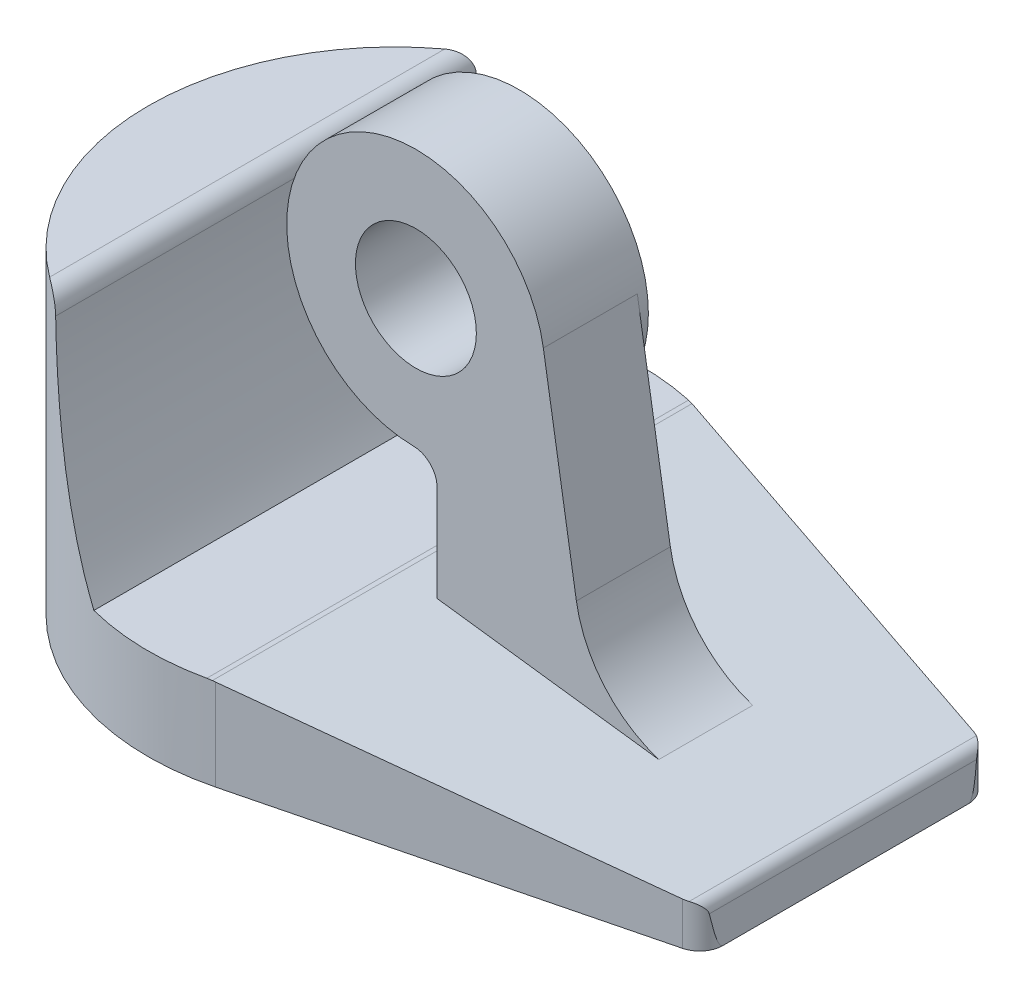
SolidWorks part; units mm, degrees
ref_plane "Front Plane" through (0, 0, 0) normal (0, 0, 1) x (1, 0, 0)
ref_plane "Top Plane" through (0, 0, 0) normal (0, 1, 0) x (1, 0, 0)
ref_plane "Right Plane" through (0, 0, 0) normal (1, 0, 0) x (0, 0, -1)
sketch "Sketch1" plane through (0, 0, 0) normal (0, 1, 0) x (1, 0, 0)
  line L0 (2.56, 10.1832) -> (18.4438, 6.1901)
  line L1 (19.2, 5.2203) -> (19.2, -5.2203)
  line L2 (18.4438, -6.1901) -> (2.56, -10.1832)
  line L3 (0, 0) -> (-30.4312, 0) construction
  circle A0 centre (0, 0) radius 10.5
  arc A1 (19.2, -5.2203) -> (18.4438, -6.1901) centre (18.2, -5.2203) cw
  arc A2 (18.4438, 6.1901) -> (19.2, 5.2203) centre (18.2, 5.2203) cw
  point P6 (19.2, 0)
  point P9 (19.2, -6)
  point P13 (19.2, 6)
  point P15 (0, -10.5)
  dimension "D1" = 21
  dimension "D4" = 1
  dimension "D3" = 29.7
  dimension "D2" = 12
extrude "Boss-Extrude1" add sketch "Sketch1" along normal blind 13.5 contours A2 L0 A0 L2 A1 L1 | A0 | A0 A1 L2 | A0 L0 A2 region at (13.6045, 0, 0) region at (0, 0, 0)
sketch "Sketch2" plane through (0, 0, 0) normal (0, 0, 1) x (1, 0, 0)
  line L0 (-10.5, 13.5) -> (-6.2826, 13.5)
  line L1 (2.56, 13.5) -> (-10.5, 13.5) construction
  line L2 (-2.65, 3.9) -> (2.2535, 3.9)
  line L3 (2.4457, 3.8876) -> (18.6485, 1.7949)
  line L5 (19.0825, 1.3426) -> (19.2, 0)
  line L6 (19.2, 13.5) -> (19.2, 0) construction
  arc A0 (-5.4834, 12.7348) -> (-2.65, 3.9) centre (12.0934, 13.5) ccw
  arc A1 (18.6485, 1.7949) -> (19.0825, 1.3426) centre (18.5844, 1.299) cw
  arc A2 (2.2535, 3.9) -> (2.4457, 3.8876) centre (2.2535, 2.4) cw
  arc A3 (-6.2826, 13.5) -> (-5.4834, 12.7348) centre (-6.2826, 12.7) cw
  point P17 (19.0475, 1.7433)
  point P20 (2.35, 3.9)
  point P22 (-5.5, 13.5)
  dimension "D6" = 0.5
  dimension "D7" = 1.5
  dimension "D8" = 0.8
  dimension "D1" = 1.7949
  dimension "D2" = 5
  dimension "D3" = 5
  dimension "D4" = 7.85
  dimension "D5" = 5
  dimension "D9" = 3.9
extrude "Cut-Extrude1" cut sketch "Sketch2" against normal through all and the other way through all
sketch "Sketch5" plane through (0, 0, 0) normal (0, 0, 1) x (1, 0, 0)
  line L0 (14.2, 2.2822) -> (17.6, 1.718)
  line L1 (2.2535, 3.9) -> (-2.65, 3.9) construction
  line L2 (17.6, 1.718) -> (17.6, 0)
  line L3 (8.5284, 15.1849) -> (9.9343, 6.56)
  line L4 (4, 8.8741) -> (4, 3.9)
  line L5 (2.56, 3.8729) -> (18.4438, 1.8213) construction
  line L6 (-10.5, 13.5) -> (-10.5, 0) construction
  line L7 (4, 3.9) -> (4, 2.2822)
  line L8 (4, 2.2822) -> (14.2, 2.2822)
  line L11 (2.2535, 3.9) -> (2.56, 3.9) construction
  circle A0 centre (3.1, 14.3) radius 5.5
  circle A1 centre (3.1, 14.3) radius 2.575
  circle A2 centre (15.0481, 7.3937) radius 5.1814
  point P2 (0, 0)
  point P20 (9.2313, 10.8725)
  point P23 (0, 0)
  point P24 (0, 0)
  point P26 (0, 0)
  point P27 (0, 0)
  point P28 (0, 0)
  point P29 (0, 0)
  point P30 (0, 0)
  point P33 (0, 0)
  point P34 (0, 0)
  point P35 (0, 0)
  dimension "D1" = 11
  dimension "D2" = 5.15
  dimension "D3" = 10.4
  dimension "D4" = 11.5
  dimension "D5" = 3.4
  dimension "D6" = 12.4
  dimension "D7" = 5.6
extrude "Boss-Extrude2" add sketch "Sketch5" against normal blind 1.8 and the other way blind 2.2 contours A2 L3 A0 L4 L7 L8 | A0 A1 region at (7.4972, 6.1482, 0) region at (8.427, 14.7313, 0)
extrude "Boss-Extrude3" add sketch "Sketch5<4>" against normal blind 2.2 contours A0 A1 region at (8.427, 14.7313, 0)
sketch "Sketch5<4>" plane through (0, 0, 0) normal (0, 0, 1) x (1, 0, 0) same geometry as "Sketch5"
fillet "Fillet1" radius 1 1 edges at (4, 8.8741, 0.2)
